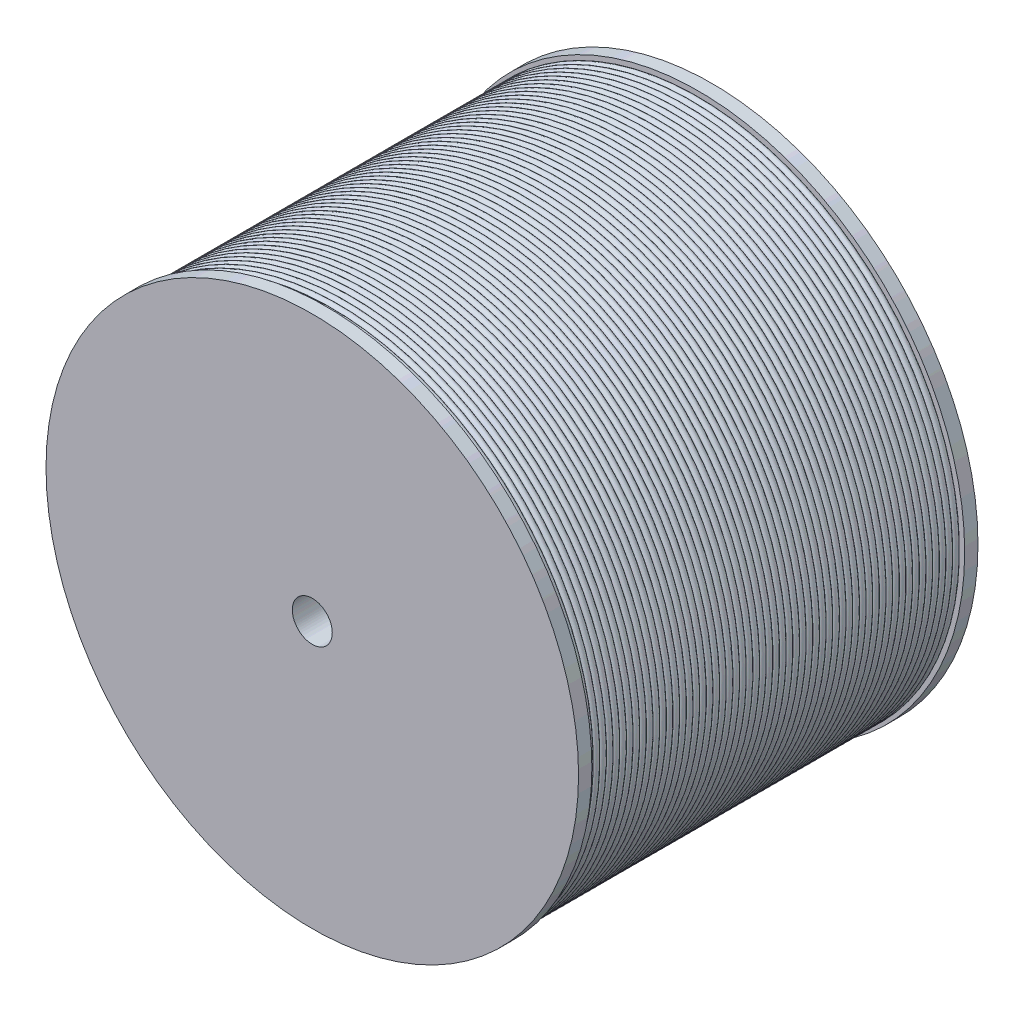
SolidWorks part; units mm, degrees
ref_plane "Спереди" through (0, 0, 0) normal (0, 0, 1) x (1, 0, 0)
ref_plane "Сверху" through (0, 0, 0) normal (0, 1, 0) x (1, 0, 0)
ref_plane "Справа" through (0, 0, 0) normal (1, 0, 0) x (0, 0, -1)
sketch "Эскиз2" plane through (0, 0, 0) normal (1, 0, 0) x (0, 0, -1)
  line L0 (0, 0) -> (0, 40)
  line L1 (0, 40) -> (2, 40)
  line L2 (2, 40) -> (2, 6)
  line L3 (2, 6) -> (58, 6)
  line L4 (58, 6) -> (58, 40)
  line L5 (58, 40) -> (60, 40)
  line L6 (60, 40) -> (60, 0)
  line L7 (0, 0) -> (60, 0) construction
  line L8 (2, 39) -> (58, 39) construction
  line L9 (60, 0) -> (0, 0)
  arc A0 (3, 39) -> (2, 39) centre (2.5, 39) ccw
  arc A1 (4, 39) -> (3, 39) centre (3.5, 39) ccw
  arc A2 (5, 39) -> (4, 39) centre (4.5, 39) ccw
  arc A3 (6, 39) -> (5, 39) centre (5.5, 39) ccw
  arc A4 (7, 39) -> (6, 39) centre (6.5, 39) ccw
  arc A5 (8, 39) -> (7, 39) centre (7.5, 39) ccw
  arc A6 (9, 39) -> (8, 39) centre (8.5, 39) ccw
  arc A7 (10, 39) -> (9, 39) centre (9.5, 39) ccw
  arc A8 (11, 39) -> (10, 39) centre (10.5, 39) ccw
  arc A9 (12, 39) -> (11, 39) centre (11.5, 39) ccw
  arc A10 (13, 39) -> (12, 39) centre (12.5, 39) ccw
  arc A11 (14, 39) -> (13, 39) centre (13.5, 39) ccw
  arc A12 (15, 39) -> (14, 39) centre (14.5, 39) ccw
  arc A13 (16, 39) -> (15, 39) centre (15.5, 39) ccw
  arc A14 (17, 39) -> (16, 39) centre (16.5, 39) ccw
  arc A15 (18, 39) -> (17, 39) centre (17.5, 39) ccw
  arc A16 (19, 39) -> (18, 39) centre (18.5, 39) ccw
  arc A17 (20, 39) -> (19, 39) centre (19.5, 39) ccw
  arc A18 (21, 39) -> (20, 39) centre (20.5, 39) ccw
  arc A19 (22, 39) -> (21, 39) centre (21.5, 39) ccw
  arc A20 (23, 39) -> (22, 39) centre (22.5, 39) ccw
  arc A21 (24, 39) -> (23, 39) centre (23.5, 39) ccw
  arc A22 (25, 39) -> (24, 39) centre (24.5, 39) ccw
  arc A23 (26, 39) -> (25, 39) centre (25.5, 39) ccw
  arc A24 (27, 39) -> (26, 39) centre (26.5, 39) ccw
  arc A25 (28, 39) -> (27, 39) centre (27.5, 39) ccw
  arc A26 (29, 39) -> (28, 39) centre (28.5, 39) ccw
  arc A27 (30, 39) -> (29, 39) centre (29.5, 39) ccw
  arc A28 (31, 39) -> (30, 39) centre (30.5, 39) ccw
  arc A29 (32, 39) -> (31, 39) centre (31.5, 39) ccw
  arc A30 (33, 39) -> (32, 39) centre (32.5, 39) ccw
  arc A31 (34, 39) -> (33, 39) centre (33.5, 39) ccw
  arc A32 (35, 39) -> (34, 39) centre (34.5, 39) ccw
  arc A33 (36, 39) -> (35, 39) centre (35.5, 39) ccw
  arc A34 (37, 39) -> (36, 39) centre (36.5, 39) ccw
  arc A35 (38, 39) -> (37, 39) centre (37.5, 39) ccw
  arc A36 (39, 39) -> (38, 39) centre (38.5, 39) ccw
  arc A37 (40, 39) -> (39, 39) centre (39.5, 39) ccw
  arc A38 (41, 39) -> (40, 39) centre (40.5, 39) ccw
  arc A39 (42, 39) -> (41, 39) centre (41.5, 39) ccw
  arc A40 (43, 39) -> (42, 39) centre (42.5, 39) ccw
  arc A41 (44, 39) -> (43, 39) centre (43.5, 39) ccw
  arc A42 (45, 39) -> (44, 39) centre (44.5, 39) ccw
  arc A43 (46, 39) -> (45, 39) centre (45.5, 39) ccw
  arc A44 (47, 39) -> (46, 39) centre (46.5, 39) ccw
  arc A45 (48, 39) -> (47, 39) centre (47.5, 39) ccw
  arc A46 (49, 39) -> (48, 39) centre (48.5, 39) ccw
  arc A47 (50, 39) -> (49, 39) centre (49.5, 39) ccw
  arc A48 (51, 39) -> (50, 39) centre (50.5, 39) ccw
  arc A49 (52, 39) -> (51, 39) centre (51.5, 39) ccw
  arc A50 (53, 39) -> (52, 39) centre (52.5, 39) ccw
  arc A51 (54, 39) -> (53, 39) centre (53.5, 39) ccw
  arc A52 (55, 39) -> (54, 39) centre (54.5, 39) ccw
  arc A53 (56, 39) -> (55, 39) centre (55.5, 39) ccw
  arc A54 (57, 39) -> (56, 39) centre (56.5, 39) ccw
  arc A55 (58, 39) -> (57, 39) centre (57.5, 39) ccw
  dimension "D6" = 1
  dimension "D1" = 12
  dimension "D2" = 2
  dimension "D3" = 60
  dimension "D4" = 40
  dimension "D5" = 1
  dimension "D7" = 56
revolve "Повернуть1" add sketch "Эскиз2" angle 360 about L9 region at (0, 20, -0.7211)
revolve "Повернуть2" add sketch "Эскиз2<4>" angle 360 about L9 region at (0, 22.6965, -30)
sketch "Эскиз2<4>" plane through (0, 0, 0) normal (1, 0, 0) x (0, 0, -1) same geometry as "Эскиз2"
sketch "Эскиз3" plane through (0, 0, 0) normal (0, 0, 1) x (1, 0, 0)
  circle A0 centre (0, 0) radius 3
  dimension "D1" = 6
extrude "Вырез-Вытянуть1" cut sketch "Эскиз3" against normal through all
